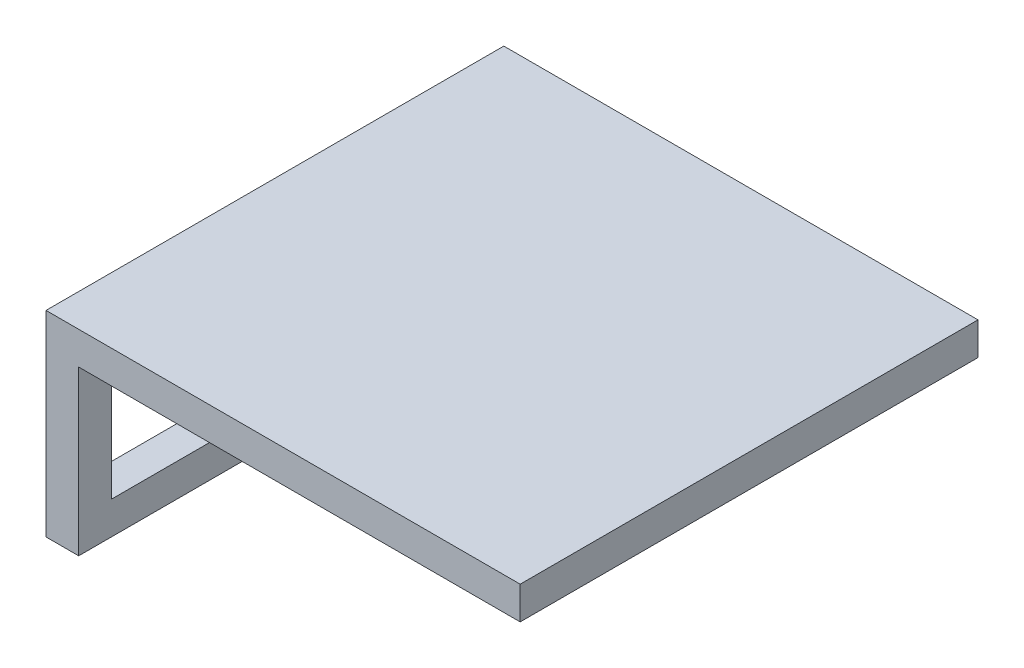
SolidWorks part; units mm, degrees
material "ABS PC"
ref_plane "Front Plane" through (0, 0, 0) normal (0, 0, 1) x (1, 0, 0)
ref_plane "Top Plane" through (0, 0, 0) normal (0, 1, 0) x (1, 0, 0)
ref_plane "Right Plane" through (0, 0, 0) normal (1, 0, 0) x (0, 0, -1)
sketch "Sketch1" plane through (0, 0, 0) normal (0, 0, 1) x (1, 0, 0)
  line L0 (67.5, 0) -> (67.5, -2) construction
  line L1 (0, 0) -> (-5, 0)
  line L2 (0, 0) -> (0, 30)
  line L3 (0, 30) -> (-5, 30)
  line L4 (-5, 0) -> (-5, 30)
  line L5 (0, 30) -> (67.5, 30)
  line L6 (0, 30) -> (0, 25)
  line L7 (0, 25) -> (67.5, 25)
  line L8 (67.5, 30) -> (67.5, 25)
  dimension "D1" = 5
  dimension "D2" = 30
  dimension "D4" = 5
extrude "Boss-Extrude1" add sketch "Sketch1" along normal mid plane 70 contours L4 L1 L2 L3 | L8 L5 L2 L7 region at (-2.5, 15, 0) region at (33.75, 27.5, 0)
sketch "Sketch2" plane through (0, 0, 0) normal (0, -1, 0) x (1, 0, 0)
  line L0 (-2.5, 10) -> (-2.5, -10) construction
  line L1 (-5, 0) -> (0, 0)
  line L2 (-5, 35) -> (-5, -35) construction
  circle A0 centre (-2.5, 10) radius 1
  circle A1 centre (-2.5, -10) radius 1
  point P9 (-2.5, 0)
  dimension "D1" = 2
  dimension "D2" = 2
  dimension "D3" = 20
extrude "Cut-Extrude1" cut sketch "Sketch2" against normal blind 10 contours A1 | A0
sketch "Sketch3" plane through (-5, 0, 0) normal (-1, 0, 0) x (0, 0, 1)
  line L0 (35, 0) -> (35, 30) construction
  line L1 (-30, 25) -> (30, 25)
  line L2 (-30, 25) -> (-30, 5)
  line L3 (-30, 5) -> (30, 5)
  line L4 (30, 25) -> (30, 5)
  line L5 (35, 0) -> (-35, 0) construction
  dimension "D1" = 20
  dimension "D2" = 60
  dimension "D3" = 5
  dimension "D4" = 5
extrude "Cut-Extrude2" cut sketch "Sketch3" against normal blind 10
